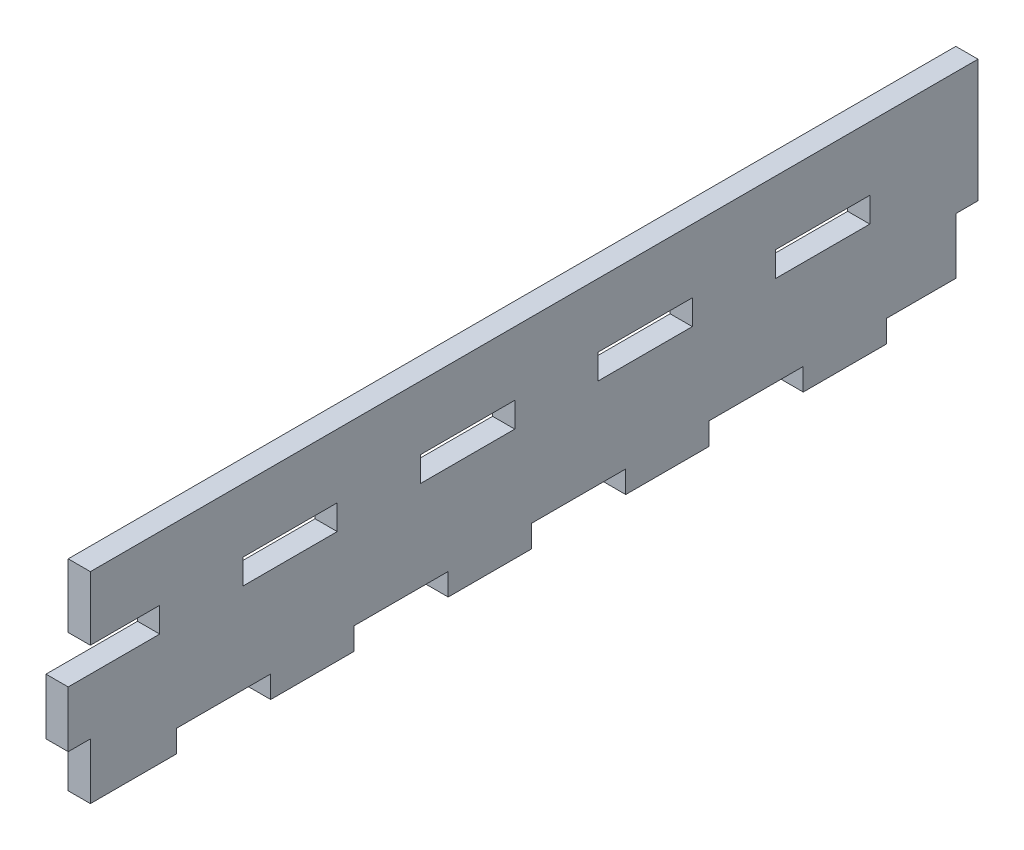
SolidWorks part; units mm, degrees
ref_plane "Plan de face" through (0, 0, 0) normal (0, 0, 1) x (1, 0, 0)
ref_plane "Plan de dessus" through (0, 0, 0) normal (0, 1, 0) x (1, 0, 0)
ref_plane "Plan de droite" through (0, 0, 0) normal (1, 0, 0) x (0, 0, -1)
sketch "Esquisse1" plane through (0, 0, 0) normal (1, 0, 0) x (0, 0, -1)
  line L5 (-41.0892, -6.055) -> (40.9108, -6.055)
  line L6 (-41.0892, -6.055) -> (-41.0892, 6.055)
  line L7 (-41.0892, 6.055) -> (40.9108, 6.055)
  line L8 (40.9108, -6.055) -> (40.9108, 6.055)
extrude "Boss.-Extru.1" add sketch "Esquisse1" along normal blind 2
sketch "Esquisse2" plane through (0, 0, 0) normal (1, 0, 0) x (0, 0, -1)
  line L0 (-33.0892, 4.055) -> (-33.0892, 6.055) construction
  line L1 (-41.3392, 6.305) -> (-32.8392, 6.305)
  line L2 (-41.3392, 6.305) -> (-41.3392, 4.055)
  line L3 (-41.3392, 4.055) -> (-32.8392, 4.055)
  line L4 (-32.8392, 6.305) -> (-32.8392, 4.055)
  line L5 (-41.0892, 6.305) -> (-41.0892, 6.055) construction
  line L6 (-41.0892, 6.055) -> (-41.3392, 6.055) construction
  line L8 (-33.0892, 5.18) -> (-32.8392, 5.18) construction
  line L9 (-41.0892, 4.055) -> (-33.0892, 4.055) construction
  line L11 (-25.3392, 6.305) -> (-16.8392, 6.305)
  line L12 (-16.8392, 6.305) -> (-16.8392, 4.055)
  line L13 (-25.3392, 4.055) -> (-16.8392, 4.055)
  line L14 (-25.3392, 6.305) -> (-25.3392, 4.055)
  line L15 (-9.3392, 6.305) -> (-0.8392, 6.305)
  line L16 (-0.8392, 6.305) -> (-0.8392, 4.055)
  line L17 (-9.3392, 4.055) -> (-0.8392, 4.055)
  line L18 (-9.3392, 6.305) -> (-9.3392, 4.055)
  line L19 (6.6608, 6.305) -> (15.1608, 6.305)
  line L20 (15.1608, 6.305) -> (15.1608, 4.055)
  line L21 (6.6608, 4.055) -> (15.1608, 4.055)
  line L22 (6.6608, 6.305) -> (6.6608, 4.055)
  line L23 (22.6608, 6.305) -> (31.1608, 6.305)
  line L24 (31.1608, 6.305) -> (31.1608, 4.055)
  line L25 (22.6608, 4.055) -> (31.1608, 4.055)
  line L26 (22.6608, 6.305) -> (22.6608, 4.055)
  line L27 (-32.8392, 4.055) -> (-25.3392, 4.055) construction
  line L29 (-25.3392, 5.18) -> (-25.0892, 5.18) construction
  line L30 (-25.0892, 6.055) -> (-25.0892, 4.055) construction
  dimension "D3" = 0.25
  dimension "D2" = 5
extrude "Enlèv. mat.-Extru.1" cut sketch "Esquisse2" along normal through all
sketch "Esquisse3" plane through (0, 0, 0) normal (1, 0, 0) x (0, 0, -1)
  line L0 (-41.0892, -6.055) -> (40.9108, -6.055) construction
  line L1 (-31.3392, -6.055) -> (-22.8392, -6.055)
  line L2 (-31.3392, -6.055) -> (-31.3392, -4.055)
  line L3 (-31.3392, -4.055) -> (-22.8392, -4.055)
  line L4 (-22.8392, -6.055) -> (-22.8392, -4.055)
  line L7 (-25.3392, 4.055) -> (-16.8392, 4.055) construction
  line L8 (-32.8392, 4.055) -> (-32.8392, 6.055) construction
  line L9 (-31.3392, -5.055) -> (-31.0892, -5.055) construction
  line L10 (-31.0892, -6.055) -> (-31.0892, -4.055) construction
  line L11 (-32.8392, 5.2908) -> (-33.0892, 5.2908) construction
  line L12 (-32.8392, 4.055) -> (-32.8392, 6.055) construction
  line L13 (-33.0892, 4.055) -> (-33.0892, 6.055) construction
  line L14 (-15.3392, -6.055) -> (-6.8392, -6.055)
  line L15 (-15.3392, -6.055) -> (-15.3392, -4.055)
  line L16 (-15.3392, -4.055) -> (-6.8392, -4.055)
  line L17 (-6.8392, -6.055) -> (-6.8392, -4.055)
  line L18 (-15.3392, -5.055) -> (-15.0892, -5.055) construction
  line L19 (0.6608, -6.055) -> (9.1608, -6.055)
  line L20 (0.6608, -6.055) -> (0.6608, -4.055)
  line L21 (0.6608, -4.055) -> (9.1608, -4.055)
  line L22 (9.1608, -6.055) -> (9.1608, -4.055)
  line L23 (0.6608, -5.055) -> (0.9108, -5.055) construction
  line L24 (16.6608, -6.055) -> (25.1608, -6.055)
  line L25 (16.6608, -6.055) -> (16.6608, -4.055)
  line L26 (16.6608, -4.055) -> (25.1608, -4.055)
  line L27 (25.1608, -6.055) -> (25.1608, -4.055)
  line L28 (16.6608, -5.055) -> (16.9108, -5.055) construction
  line L29 (32.6608, -6.055) -> (41.1608, -6.055)
  line L30 (32.6608, -6.055) -> (32.6608, -4.055)
  line L31 (32.6608, -4.055) -> (41.1608, -4.055)
  line L32 (41.1608, -6.055) -> (41.1608, -4.055)
  line L33 (32.6608, -5.055) -> (32.9108, -5.055) construction
  line L40 (48.6608, -6.055) -> (57.1608, -6.055) [skipped]
  line L41 (48.6608, -6.055) -> (48.6608, -4.055) [skipped]
  line L42 (48.6608, -4.055) -> (57.1608, -4.055) [skipped]
  line L43 (48.6608, -5.055) -> (48.9108, -5.055) construction
  line L44 (57.1608, -6.055) -> (57.1608, -4.055) [skipped]
  line L45 (40.9108, -6.055) -> (40.9108, -4.055) construction
  dimension "D2" = 0.25
  dimension "D1" = 6
extrude "Enlèv. mat.-Extru.2" cut sketch "Esquisse3" along normal through all
sketch "Esquisse4" plane through (2, 0, 0) normal (1, 0, 0) x (0, 0, -1)
  line L0 (-39.0892, -1) -> (-39.0892, 4.055) construction
  line L1 (-41.0892, -6.055) -> (-39.0892, -6.055)
  line L2 (-41.0892, -6.055) -> (-41.0892, -1)
  line L3 (-41.0892, -1) -> (-39.0892, -1)
  line L4 (-39.0892, -6.055) -> (-39.0892, -1)
  line L5 (-41.0892, 4.055) -> (-33.0892, 4.055) construction
  line L6 (-41.0892, 6.055) -> (-41.0892, 4.055) construction
  line L8 (40.9108, -4.055) -> (38.9108, -4.055)
  line L9 (40.9108, -4.055) -> (40.9108, 1)
  line L10 (40.9108, 1) -> (38.9108, 1)
  line L11 (38.9108, -4.055) -> (38.9108, 1)
extrude "Enlèv. mat.-Extru.3" cut sketch "Esquisse4" against normal through all
sketch "Esquisse5" plane through (0, 0, 0) normal (-1, 0, 0) x (0, 0, 1)
  line L0 (39.0892, -6.055) -> (39.0892, -1) construction
  line L1 (-40.9108, 6.055) -> (39.0892, 6.055)
  line L2 (-40.9108, 6.055) -> (-40.9108, 12.055)
  line L3 (-40.9108, 12.055) -> (39.0892, 12.055)
  line L4 (39.0892, 6.055) -> (39.0892, 12.055)
  dimension "D1" = 6
extrude "Boss.-Extru.2" add sketch "Esquisse5" against normal blind 2
sketch "Esquisse6" plane through (2, 0, 0) normal (1, 0, 0) x (0, 0, -1)
  line L0 (31.1608, 4.055) -> (31.1608, 6.055) construction
  line L1 (-32.8392, 6.305) -> (-39.0892, 6.305)
  line L2 (-32.8392, 6.305) -> (-32.8392, 6.055)
  line L3 (-32.8392, 6.055) -> (-39.0892, 6.055)
  line L4 (-39.0892, 6.305) -> (-39.0892, 6.055)
  line L5 (-25.3392, 6.055) -> (-16.8392, 6.055)
  line L6 (-25.3392, 6.055) -> (-25.3392, 6.305)
  line L7 (-25.3392, 6.305) -> (-16.8392, 6.305)
  line L8 (-16.8392, 6.055) -> (-16.8392, 6.305)
  line L9 (-9.3392, 6.055) -> (-0.8392, 6.055)
  line L10 (-9.3392, 6.055) -> (-9.3392, 6.305)
  line L11 (-9.3392, 6.305) -> (-0.8392, 6.305)
  line L12 (-0.8392, 6.055) -> (-0.8392, 6.305)
  line L13 (6.6608, 6.055) -> (15.1608, 6.055)
  line L14 (6.6608, 6.055) -> (6.6608, 6.305)
  line L15 (6.6608, 6.305) -> (15.1608, 6.305)
  line L16 (15.1608, 6.055) -> (15.1608, 6.305)
  line L17 (22.6608, 6.055) -> (31.1608, 6.055)
  line L18 (22.6608, 6.055) -> (22.6608, 6.305)
  line L19 (22.6608, 6.305) -> (31.1608, 6.305)
  line L20 (31.1608, 6.055) -> (31.1608, 6.305)
  line L21 (31.1608, 6.055) -> (22.6608, 6.055) construction
  line L22 (15.1608, 4.055) -> (15.1608, 6.055) construction
  line L23 (15.1608, 6.055) -> (6.6608, 6.055) construction
  line L24 (-16.8392, 6.055) -> (-25.3392, 6.055) construction
  point P25 (31.1608, 6.055)
  point P30 (15.1608, 6.055)
  point P35 (-0.8392, 6.055)
  point P37 (-17.0762, 6.055)
  point P40 (-16.8392, 6.055)
  point P42 (-32.8392, 6.055)
  dimension "D1" = 0.25
extrude "Enlèv. mat.-Extru.4" cut sketch "Esquisse6" against normal through all
